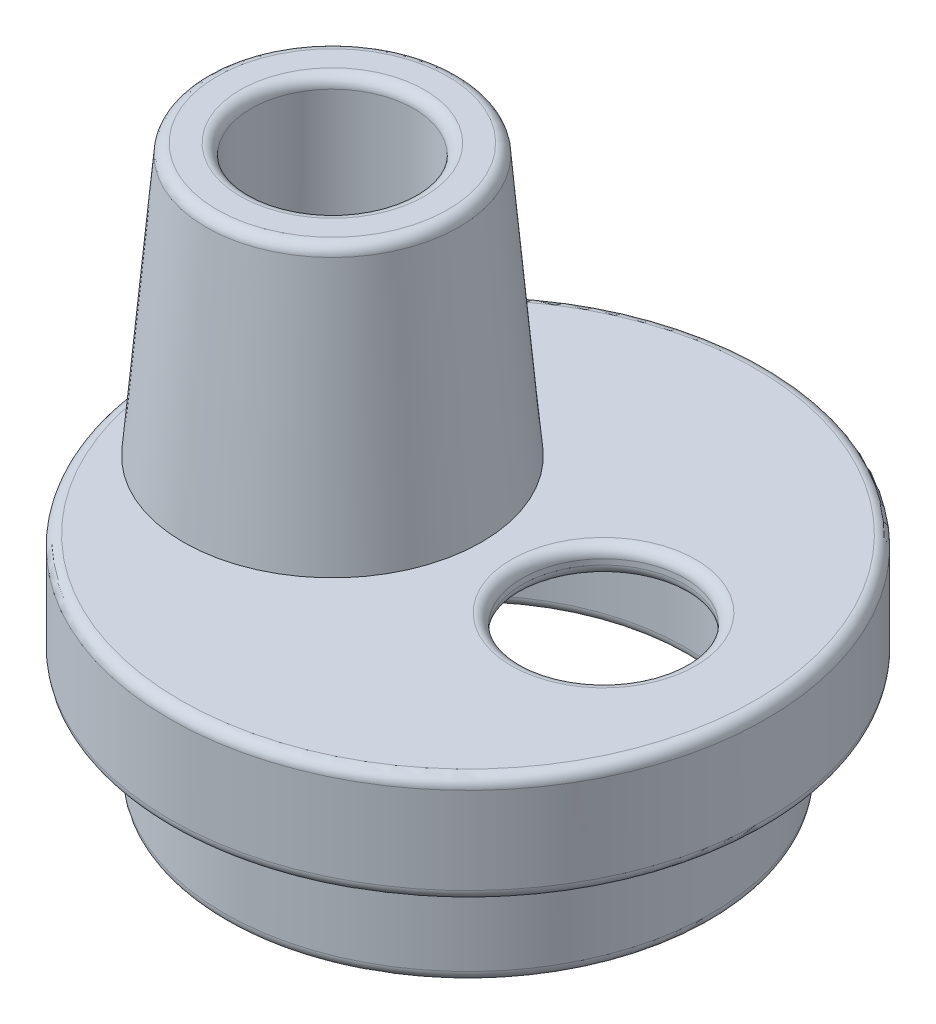
SolidWorks part; units mm, degrees
ref_plane "Front Plane" through (0, 0, 0) normal (0, 0, 1) x (1, 0, 0)
ref_plane "Top Plane" through (0, 0, 0) normal (0, 1, 0) x (1, 0, 0)
ref_plane "Right Plane" through (0, 0, 0) normal (1, 0, 0) x (0, 0, -1)
sketch "Sketch1" plane through (0, 0, 0) normal (1, 0, 0) x (0, 0, -1)
  line L0 (-5.5, -2) -> (-4.5, -2)
  line L1 (0, 0) -> (-5.5, 0)
  line L2 (0, 0) -> (0, -4) construction
  line L3 (0, -0.5) -> (-5, -0.5)
  line L4 (-5.5, 0) -> (-5.5, -2)
  line L5 (-5, -0.5) -> (-5, -1.5)
  line L6 (-5, -1.5) -> (-4, -1.5)
  line L7 (0, -4) -> (-4.5, -4) construction
  line L8 (-4.5, -2) -> (-4.5, -4)
  line L9 (-4, -1.5) -> (-4, -4)
  line L10 (0, -0.5) -> (0, 0)
  line L11 (-4, -4) -> (-4.5, -4)
  dimension "D1" = 5.5
  dimension "D2" = 2
  dimension "D3" = 4.5
  dimension "D4" = 4
  dimension "D5" = 0.5
revolve "Revolve1" add sketch "Sketch1" angle 360 about L2
sketch "Sketch2" plane through (0, 0, 0) normal (0, 1, 0) x (1, 0, 0)
  line L0 (0, 5.5) -> (0, -5.5) construction
  line L1 (-5.5, 0) -> (5.5, 0) construction
  circle A0 centre (0, 0) radius 5.5 construction
  circle A1 centre (2.5, 0) radius 1.5
  circle A2 centre (-2.5, 0) radius 1.5
  dimension "D1" = 3
  dimension "D2" = 2.5
extrude "Cut-Extrude1" cut sketch "Sketch2" against normal up to next
sketch "Sketch3" plane through (0, 0, 0) normal (0, 1, 0) x (1, 0, 0)
  line L0 (0, 0) -> (-2.5, 0) construction
  circle A0 centre (-2.5, 0) radius 1.5
  circle A1 centre (-2.5, 0) radius 2.75
  dimension "D2" = 3
  dimension "D3" = 5.5
  dimension "D1" = 2.5
extrude "Boss-Extrude1" add sketch "Sketch3" along normal blind 5
draft "Draft2" type of draft neutral plane draft angle 5 faces to draft 1 face at (-2.5, 5, 2.75) neutral plane through (0, 0, 0) neutral plane normal (0, 1, 0) parameters "D1"=5
fillet "Fillet1" radius 0.2 9 edges at (-2.5, -0.5, -1.5) (0, -4, 4) (0, -4, 4.5) (0, -2, 5.5) (2.5, -0.5, -1.5) (2.5, 0, 1.5) (-2.5, 5, 2.3126) (-2.5, 5, 1.5) (0, 0, 5.5)
